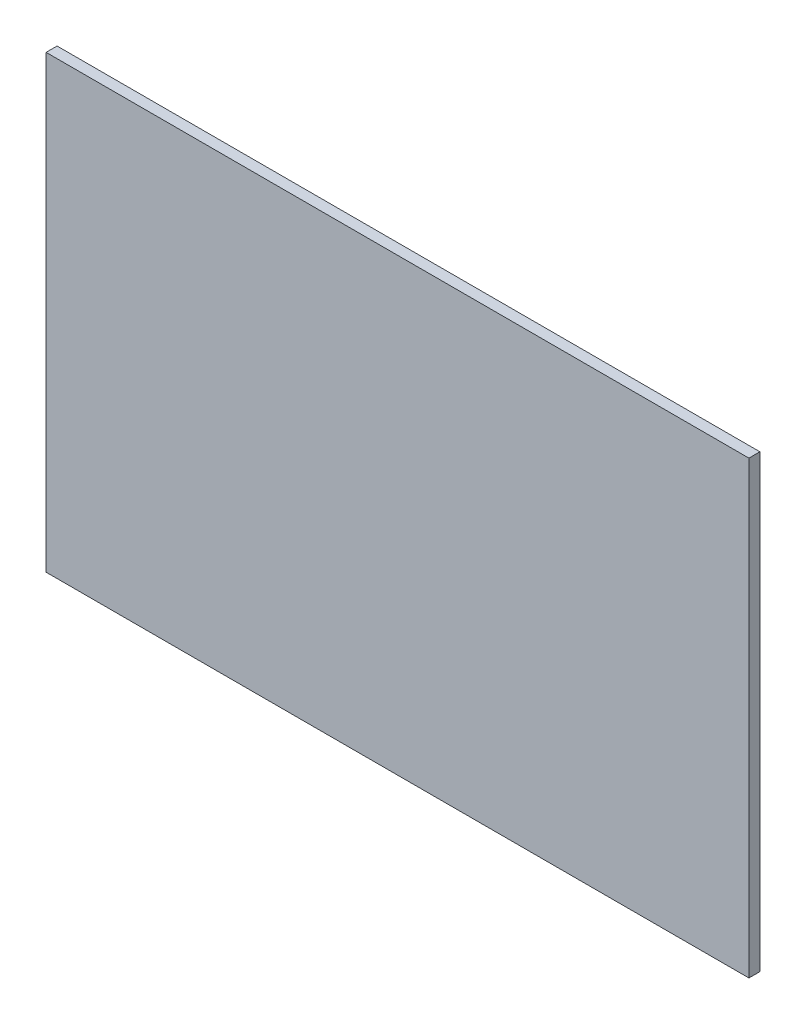
SolidWorks part; units mm, degrees
material "Oak"
ref_plane "Front Plane" through (0, 0, 0) normal (0, 0, 1) x (1, 0, 0)
ref_plane "Top Plane" through (0, 0, 0) normal (0, 1, 0) x (1, 0, 0)
ref_plane "Right Plane" through (0, 0, 0) normal (1, 0, 0) x (0, 0, -1)
sketch "Sketch1" plane through (0, 0, 0) normal (0, 0, 1) x (1, 0, 0)
  line L1 (-160, 102.5) -> (160, 102.5)
  line L2 (-160, 102.5) -> (-160, -102.5)
  line L3 (-160, -102.5) -> (160, -102.5)
  line L4 (160, 102.5) -> (160, -102.5)
  line L5 (-160, 102.5) -> (160, -102.5) construction
  line L6 (-160, -102.5) -> (160, 102.5) construction
  point P0 (0, 0)
  dimension "D1" = 320
  dimension "D2" = 205
base flange "Base-Flange1" sketch "Sketch1" thickness 5 reverse thickness direction no parameters "D1"=0.7366
sketch "Bend-Lines1" [suppressed] plane through (0, 0, 0) normal (0, 1, 0) x (1, 0, 0)
sketch "Bounding-Box1" [suppressed] plane through (0, 0, 0) normal (0, 1, 0) x (1, 0, 0)
sheet metal parameters "Sheet-Metal1" thickness 5 parameters "D1"=0.7366
flat pattern "Flat-Pattern1" [suppressed]
sketch "Bend-Lines2" plane through (0, 0, 0) normal (0, 1, 0) x (1, 0, 0)
sketch3d "Bounding-Box2" [suppressed]
  line L0 (160, -102.5, 0) -> (-160, -102.5, 0) construction
  line L1 (160, 102.5, 0) -> (-160, 102.5, 0) construction
  line L2 (160, -102.5, 0) -> (160, 102.5, 0) construction
  line L3 (-160, -102.5, 0) -> (-160, 102.5, 0) construction
